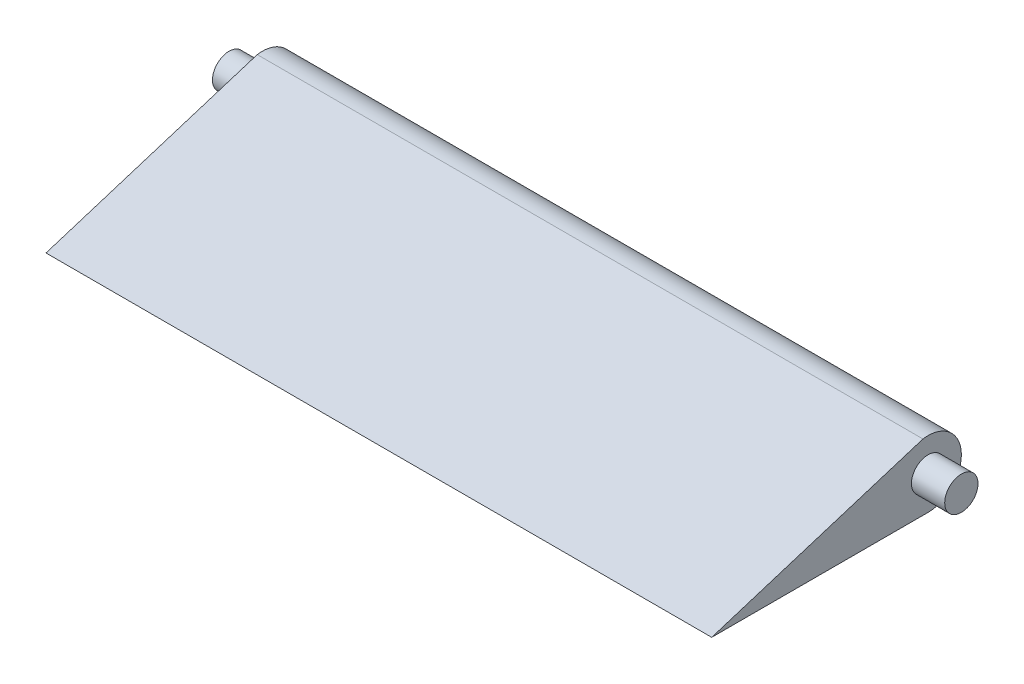
SolidWorks part; units mm, degrees
ref_plane "Front Plane" through (0, 0, 0) normal (0, 0, 1) x (1, 0, 0)
ref_plane "Top Plane" through (0, 0, 0) normal (0, 1, 0) x (1, 0, 0)
ref_plane "Right Plane" through (0, 0, 0) normal (1, 0, 0) x (0, 0, -1)
sketch "Sketch2" plane through (0, 0, 0) normal (1, 0, 0) x (0, 0, -1)
  line L0 (0, -25.4) -> (-165.1, -25.4)
  line L3 (-165.1, -25.4) -> (-3.9077, 25.0976)
  circle A0 centre (0, 0) radius 12.7
  arc A1 (0, -25.4) -> (-3.9077, 25.0976) centre (0, 0) ccw
  dimension "D1" = 165.1
  dimension "D2" = 25.4
  dimension "D3" = 25.4
extrude "Boss-Extrude2" add sketch "Sketch2" along normal blind 508
ref_plane "Plane1" through (254, 0, 0) normal (-1, 0, 0) x (0, 0, 1)
sketch "Sketch3" plane through (254, 0, 0) normal (-1, 0, 0) x (0, 0, 1)
  circle A0 centre (0, 0) radius 12.7
  dimension "D1" = 25.4
extrude "Boss-Extrude3" add sketch "Sketch3" along normal mid plane 558.8
